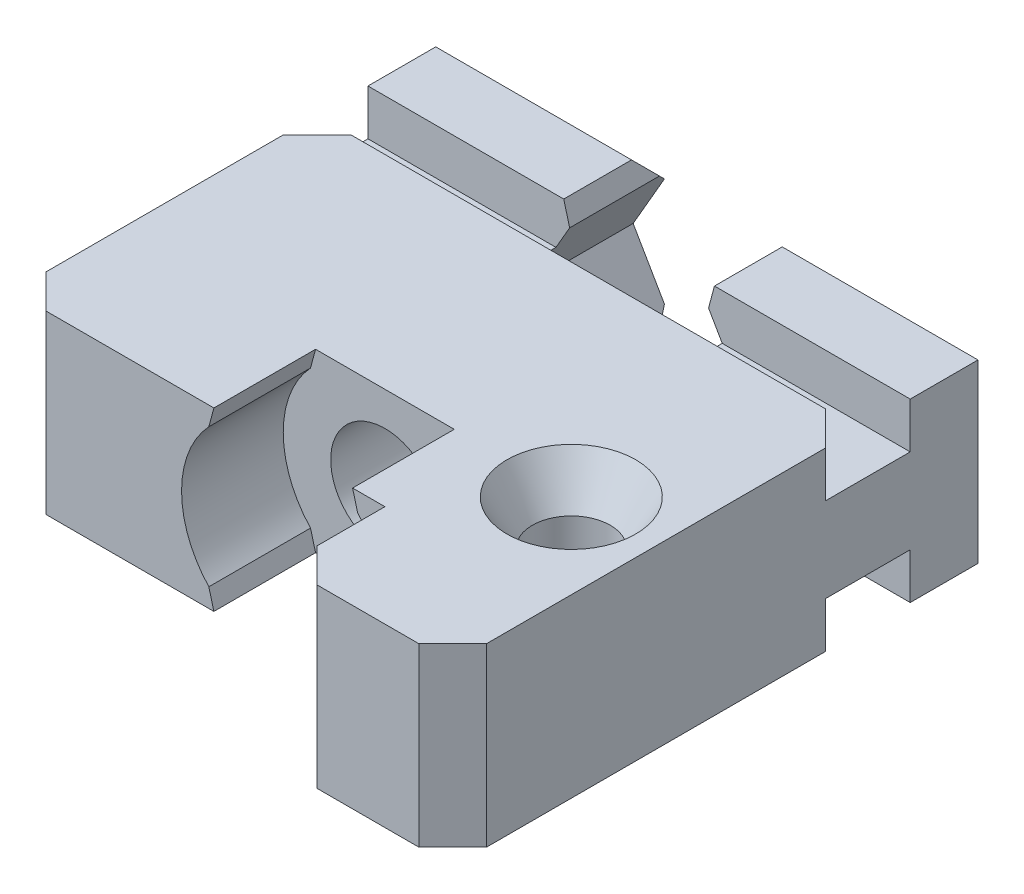
SolidWorks part; units mm, degrees
ref_plane "Front Plane" through (0, 0, 0) normal (0, 0, 1) x (1, 0, 0)
ref_plane "Top Plane" through (0, 0, 0) normal (0, 1, 0) x (1, 0, 0)
ref_plane "Right Plane" through (0, 0, 0) normal (1, 0, 0) x (0, 0, -1)
sketch "Sketch1" plane through (0, 0, 0) normal (0, 1, 0) x (1, 0, 0)
  line L0 (0, 0) -> (16, 0)
  line L1 (16, 0) -> (16, -12)
  line L2 (16, -12) -> (11, -12)
  line L3 (11, -12) -> (11, -9)
  line L4 (11, -9) -> (0, -9)
  line L5 (0, -9) -> (0, 0)
  circle A0 centre (13.5, -6) radius 1.15
  point P9 (13.5, -12)
  point P10 (16, -6)
  dimension "D5" = 2.3
  dimension "D1" = 16
  dimension "D2" = 9
  dimension "D3" = 12
  dimension "D4" = 5
extrude "Boss-Extrude1" add sketch "Sketch1" along normal mid plane 5.2
sketch "Sketch2" plane through (0, 0, 0) normal (-1, 0, 0) x (0, 0, 1)
  line L0 (-1.5, -1.25) -> (-1.5, -2.6)
  line L1 (-4.5, 2.6) -> (-1.5, 2.6)
  line L2 (-4.5, 2.6) -> (-4.5, -2.6)
  line L3 (-4.5, -2.6) -> (-1.5, -2.6)
  line L4 (-1.5, 2.6) -> (-1.5, 1.25)
  line L5 (-1.5, 1.25) -> (0, 1.25)
  line L6 (0, -2.6) -> (9, -2.6) construction
  line L7 (-1.5, -1.25) -> (0, -1.25)
  line L8 (0, 1.25) -> (0, -1.25)
  line L9 (0, 2.6) -> (9, 2.6) construction
  point P4 (0, 0)
  dimension "D1" = 2.5
  dimension "D2" = 1.5
  dimension "D3" = 3
extrude "Boss-Extrude2" add sketch "Sketch2" against normal up to surface (16 mm away) up to face at (16, 0, 6)
sketch "Sketch3" plane through (0, 0, -4.5) normal (0, 0, -1) x (-1, 0, 0)
  line L0 (-16, 2.6) -> (0, 2.6) construction
  line L1 (0, 2.6) -> (0, -2.6) construction
  circle A0 centre (-8, 0) radius 1.6
  point P4 (-8, 2.6)
  point P7 (0, 0)
  dimension "D1" = 3.2
extrude "Cut-Extrude1" cut sketch "Sketch3" against normal through all
sketch "Sketch4" plane through (0, 0, 9) normal (0, 0, 1) x (1, 0, 0)
  circle A0 centre (8, 0) radius 3
  dimension "D1" = 6
extrude "Cut-Extrude2" cut sketch "Sketch4" against normal blind 3
sketch "Sketch5" plane through (0, 0, -4.5) normal (0, 0, -1) x (-1, 0, 0)
  line L1 (-4.8246, 0) -> (-6.4123, 2.75)
  line L2 (-6.4123, 2.75) -> (-9.5877, 2.75)
  line L3 (-9.5877, 2.75) -> (-11.1754, 0)
  line L4 (-11.1754, 0) -> (-9.5877, -2.75)
  line L5 (-9.5877, -2.75) -> (-6.4123, -2.75)
  line L6 (-6.4123, -2.75) -> (-4.8246, 0)
  circle A0 centre (-8, 0) radius 2.75 construction
  circle A1 centre (-8, 0) radius 1.6 construction
  dimension "D1" = 5.5
extrude "Cut-Extrude3" cut sketch "Sketch5" against normal up to surface (4.5 mm away) up to face at (9.1669, 1.9833, 0)
chamfer "Chamfer1" distance 0.75 angle 45 8 edges at (9.4967, 2.6, 7.5) (6.5033, 2.6, 7.5) (9.4967, -2.6, 7.5) (6.5033, -2.6, 7.5) (9.6743, 2.6, -3) (6.3257, 2.6, -3) (6.3257, -2.6, -3) (9.6743, -2.6, -3)
chamfer "Chamfer2" distance 1 angle 45 13 edges at (16, 0, 12) (11, 0, 12) (0, 0, 9) (2.8883, -2.6, -4.5) (0, 0, -4.5) (16, 0, -4.5) (2.8883, 2.6, -4.5) (13.1117, -2.6, -4.5) (13.1117, 2.6, -4.5)
chamfer "Chamfer3" distance 0.75 angle 60 2 edges at (13.5, -2.6, 7.15) (13.5, 2.6, 7.15)
